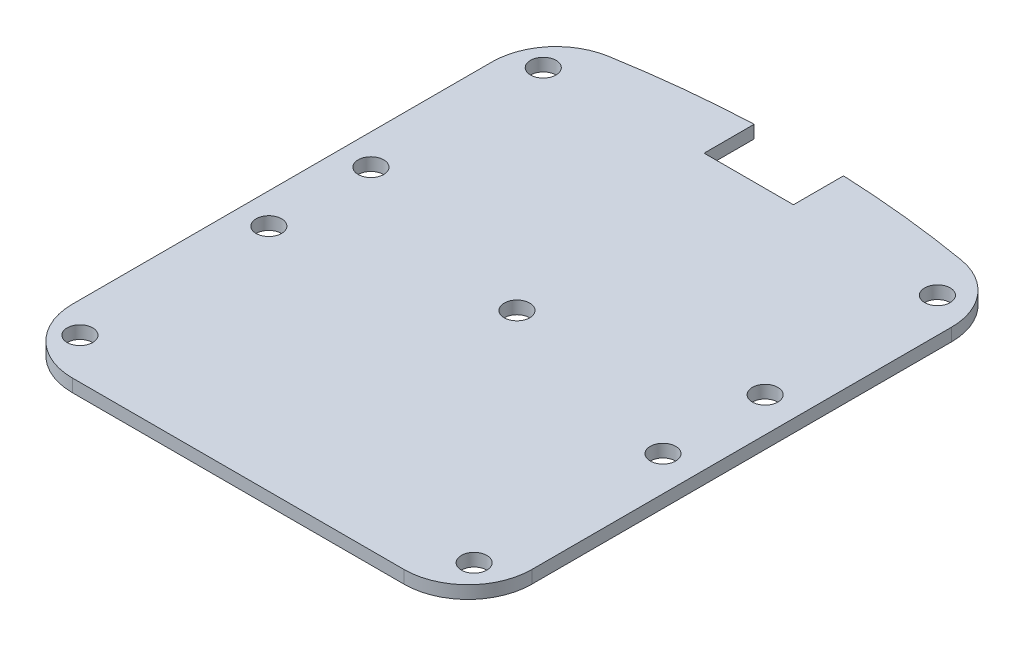
SolidWorks part; units mm, degrees
ref_plane "Front Plane" through (0, 0, 0) normal (0, 0, 1) x (1, 0, 0)
ref_plane "Top Plane" through (0, 0, 0) normal (0, 1, 0) x (1, 0, 0)
ref_plane "Right Plane" through (0, 0, 0) normal (1, 0, 0) x (0, 0, -1)
sketch "Sketch1" plane through (0, 0, 0) normal (0, 1, 0) x (1, 0, 0)
  line L1 (-64.2024, -110) -> (65.7976, -110)
  line L5 (-89.2024, -35) -> (-89.2024, -85)
  line L6 (90.7976, -35) -> (90.7976, -85)
  line L7 (-89.2024, 79.4733) -> (-89.2024, 31.4733)
  line L20 (90.7976, 31.4733) -> (90.7976, 79.4617)
  line L30 (-89.2024, -35) -> (-89.2024, 31.4733)
  line L31 (90.7976, -35) -> (90.7976, 31.4733)
  arc A0 (-68.4209, 104.1148) -> (70.0206, 104.1024) centre (0.7637, -300.0058) cw
  arc A1 (65.7976, -110) -> (90.7976, -85) centre (65.7976, -85) ccw
  arc A2 (-64.2024, -110) -> (-89.2024, -85) centre (-64.2024, -85) cw
  arc A3 (90.7976, 79.4617) -> (70.0206, 104.1024) centre (65.7976, 79.4617) ccw
  arc A4 (-89.2024, 79.4733) -> (-68.4209, 104.1148) centre (-64.2024, 79.4733) cw
  point P0 (0, 0)
  point P25 (-0.7976, 109.9942)
  dimension "D3" = 25
  dimension "D4" = 25
extrude "Boss-Extrude1" add sketch "Sketch1" along normal blind 5 contours A4 L30 A2 L1 A1 L31 A3 A0 region at (0.7967, 0, 1.3605)
sketch "Sketch5" plane through (0, 5, 0) normal (0, 1, 0) x (1, 0, 0)
  line L1 (-89.2024, -85) -> (-89.2024, 79.4733) construction
  circle A0 centre (-77.2024, 20) radius 5
  circle A1 centre (-77.2024, -20) radius 5
  circle A2 centre (-77.2024, 87.5) radius 5
  circle A3 centre (-77.2024, -94) radius 5
  circle A4 centre (0, 0) radius 5
  circle A5 centre (77.2024, -94) radius 5
  circle A6 centre (77.2024, -20) radius 5
  circle A7 centre (77.2024, 20) radius 5
  circle A8 centre (77.2024, 87.5) radius 5
  dimension "D2" = 12
  dimension "D6" = 67.5
  dimension "D8" = 10
  dimension "D5" = 12
extrude "Cut-Extrude2" cut sketch "Sketch5" against normal blind 10
sketch "Sketch6" plane through (0, 0, 0) normal (0, -1, 0) x (1, 0, 0)
  line L2 (-40, -90) -> (40, -90)
  line L3 (-40, -90) -> (-40, -10)
  line L4 (-40, -10) -> (40, -10)
  line L5 (40, -90) -> (40, -10)
  line L6 (-40, -90) -> (40, -10) construction
  line L7 (-40, -10) -> (40, -90) construction
  line L9 (-47.5, 12.5) -> (47.5, 12.5)
  line L10 (-47.5, 12.5) -> (-47.5, 107.5)
  line L11 (-47.5, 107.5) -> (47.5, 107.5)
  line L12 (47.5, 12.5) -> (47.5, 107.5)
  line L13 (-47.5, 12.5) -> (47.5, 107.5) construction
  line L14 (-47.5, 107.5) -> (47.5, 12.5) construction
  point P3 (0, -50)
  point P9 (0, 60)
  dimension "D1" = 80
  dimension "D2" = 80
  dimension "D4" = 95
  dimension "D5" = 95
extrude "Boss-Extrude2" add sketch "Sketch6" along normal blind 1
sketch "Sketch7" plane through (0, 0, 0) normal (0, -1, 0) x (1, 0, 0)
  line L3 (-40, -90) -> (40, -90) construction
  line L4 (-16.6996, -121.4032) -> (18.3004, -121.4032)
  line L5 (-16.6996, -121.4032) -> (-16.6996, -90)
  line L6 (-16.6996, -90) -> (18.3004, -90)
  line L7 (18.3004, -121.4032) -> (18.3004, -90)
  line L8 (-16.6996, -121.4032) -> (18.3004, -90) construction
  line L9 (-16.6996, -90) -> (18.3004, -121.4032) construction
  point P5 (0.8004, -105.7016)
  dimension "D1" = 35
extrude "Cut-Extrude3" cut sketch "Sketch7" against normal blind 10
